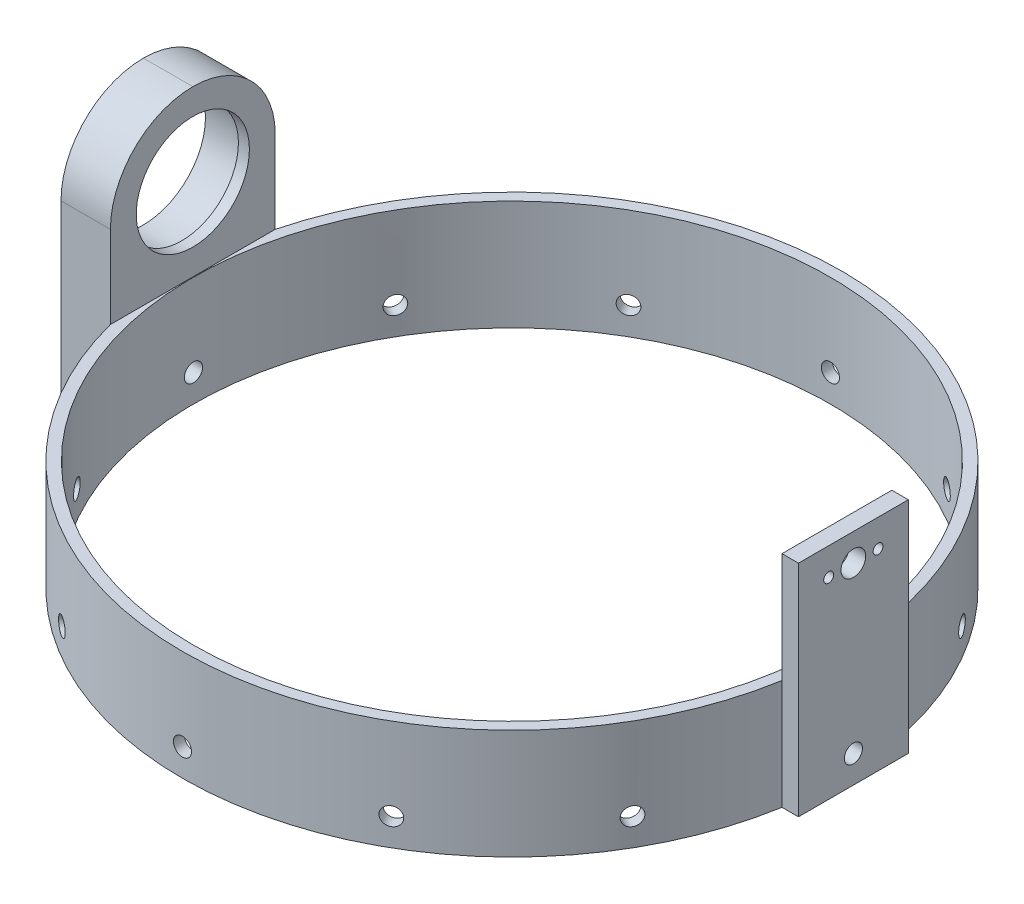
SolidWorks part; units mm, degrees
ref_plane "Front Plane" through (0, 0, 0) normal (0, 0, 1) x (1, 0, 0)
ref_plane "Top Plane" through (0, 0, 0) normal (0, 1, 0) x (1, 0, 0)
ref_plane "Right Plane" through (0, 0, 0) normal (1, 0, 0) x (0, 0, -1)
sketch "Sketch1" plane through (0, 0, 0) normal (0, 1, 0) x (1, 0, 0)
  circle A0 centre (0, 0) radius 58
  circle A1 centre (0, 0) radius 60
  dimension "D1" = 116
  dimension "D2" = 2
extrude "Boss-Extrude1" add sketch "Sketch1" along normal blind 20
sketch "Sketch2" plane through (0, 20, 0) normal (0, 1, 0) x (1, 0, 0)
  line L1 (59.1608, 10) -> (62.1608, 10)
  line L2 (59.1608, 10) -> (59.1608, -10)
  line L3 (59.1608, -10) -> (62.1608, -10)
  line L4 (62.1608, 10) -> (62.1608, -10)
  circle A0 centre (0, 0) radius 60 construction
  point P6 (0, 0)
  dimension "D1" = 20
  dimension "D2" = 3
extrude "Boss-Extrude2" add sketch "Sketch2" along normal blind 20 and the other way up to surface (20 mm away) other way up to face at (0, 0, 60)
sketch "Sketch3" plane through (59.1608, 0, 0) normal (-1, 0, 0) x (0, 0, 1)
  line L0 (0, 40) -> (0, 20) construction
  line L1 (-10, 40) -> (10, 40) construction
  line L2 (-10, 20) -> (10, 20) construction
  line L3 (-4.5, 35) -> (4.5, 35) construction
  circle A0 centre (0, 35) radius 2.25
  circle A1 centre (-4.5, 35) radius 0.9
  circle A2 centre (4.5, 35) radius 0.9
  point P9 (0, 35)
  dimension "D1" = 4.5
  dimension "D2" = 1.8
  dimension "D3" = 1.8
  dimension "D4" = 9
  dimension "D5" = 15
extrude "Cut-Extrude1" cut sketch "Sketch3" against normal up to surface (3 mm away) up to face at (62.1608, 20, 0)
sketch "Sketch4" plane through (0, 20, 0) normal (0, 1, 0) x (1, 0, 0)
  line L1 (-58.0948, 15) -> (-67.0948, 15)
  line L2 (-58.0948, 15) -> (-58.0948, -15)
  line L3 (-58.0948, -15) -> (-67.0948, -15)
  line L4 (-67.0948, 15) -> (-67.0948, -15)
  arc A0 (59.1608, 10) -> (59.1608, -10) centre (0, 0) ccw construction
  point P7 (0, 0)
  dimension "D1" = 30
  dimension "D2" = 9
extrude "Boss-Extrude3" add sketch "Sketch4" along normal blind 30 and the other way up to surface (20 mm away) other way up to face at (30.8706, 0, 0)
sketch "Sketch5" plane through (-58.0948, 0, 0) normal (1, 0, 0) x (0, 0, -1)
  circle A0 centre (0, 35) radius 2.25 construction
  circle A1 centre (0, 35) radius 2.25 construction
  circle A2 centre (0, 35) radius 11.3
  dimension "D1" = 22.6
extrude "Cut-Extrude2" cut sketch "Sketch5" against normal through all
sketch "Sketch7" plane through (-58.0948, 0, 0) normal (1, 0, 0) x (0, 0, -1)
  circle A0 centre (0, 35) radius 11.3 construction
  circle A1 centre (0, 35) radius 11.3
  circle A2 centre (0, 35) radius 10.3
  dimension "D1" = 1
extrude "Boss-Extrude4" add sketch "Sketch7" against normal blind 2
fillet "Fillet1" radius 15 2 edges at (-62.5948, 50, -15) (-62.5948, 50, 15)
sketch "Sketch8" plane through (0, 0, 0) normal (1, 0, 0) x (0, 0, -1)
  line L0 (0, 0) -> (0, 5) construction
  circle A0 centre (0, 5) radius 1.65
  dimension "D2" = 3.3
  dimension "D1" = 5
extrude "Cut-Extrude3" cut sketch "Sketch8" against normal through all
pattern_circular "CirPattern1" count 12 over 360 about axis through (0, 20, 0) along (0, -1, 0) of "Cut-Extrude3"
